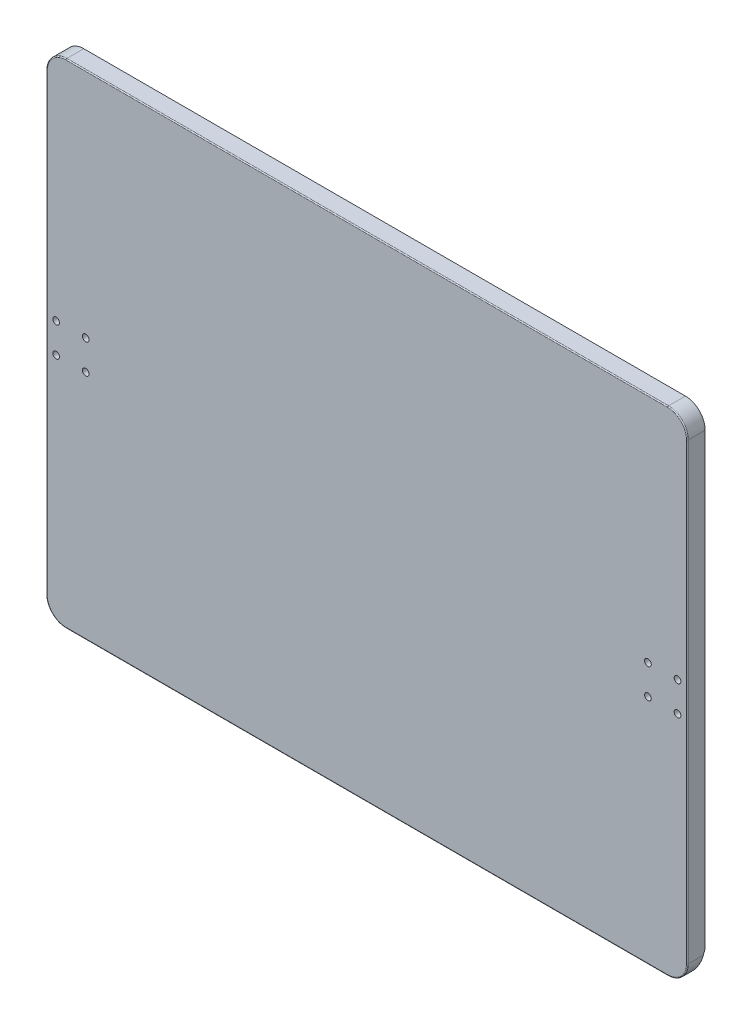
SolidWorks part; units mm, degrees
material "Beech"
ref_plane "Front Plane" through (0, 0, 0) normal (0, 0, 1) x (1, 0, 0)
ref_plane "Top Plane" through (0, 0, 0) normal (0, 1, 0) x (1, 0, 0)
ref_plane "Right Plane" through (0, 0, 0) normal (1, 0, 0) x (0, 0, -1)
sketch "Sketch1" plane through (0, 0, 0) normal (0, 0, 1) x (1, 0, 0)
  line L1 (0, 0) -> (650, 0)
  line L2 (0, 0) -> (0, 500)
  line L3 (0, 500) -> (650, 500)
  line L4 (650, 0) -> (650, 500)
  dimension "D1" = 500
  dimension "D2" = 650
extrude "base" add sketch "Sketch1" along normal blind 18
hole_wizard "counterbored M5 bolt holes" positions "Sketch2" profile "Sketch3" hole size "1/4" standard "ANSI Inch" end condition through all
sketch "Sketch2" plane through (0, 0, 18) normal (0, 0, 1) x (1, 0, 0)
  line L1 (10, 265) -> (40, 265)
  line L2 (10, 265) -> (10, 235)
  line L3 (10, 235) -> (40, 235)
  line L4 (40, 265) -> (40, 235)
  line L5 (10, 250) -> (0, 250)
  line L6 (0, 500) -> (0, 0) construction
  point P1 (10, 265)
  point P2 (40, 235)
  point P41 (10, 235)
  point P42 (40, 265)
  dimension "D1" = 30
  dimension "D2" = 30
  dimension "D3" = 10
sketch "Sketch3" plane through (10, 265, 18) normal (1, 0, 0) x (0, -1, 0)
  line L0 (0, 0) -> (0, 18)
  line L1 (0, 18) -> (3.3782, 18)
  line L2 (3.3782, 18) -> (3.3782, 0)
  line L5 (3.3782, 0) -> (0, 0)
  line L11 (0, -6.35) -> (0, 107.95) construction
  dimension "Thru Hole Dia." = 6.7564
  dimension "Thru Hole Depth" = 18
ref_plane "midplane in x" through (325, 0, 0) normal (-1, 0, 0) x (0, 0, 1)
mirror "mirror counterbored bolt holes" about plane through (325, 0, 0) normal (-1, 0, 0) of "counterbored M5 bolt holes"
fillet "round corners" radius 20 4 edges at (0, 500, 9) (650, 500, 9) (650, 0, 9) (0, 0, 9)
fillet "break top edge" radius 1 8 edges at (5.8579, 494.1421, 18) (325, 500, 18) (644.1421, 494.1421, 18) (650, 250, 18) (644.1421, 5.8579, 18) (325, 0, 18) (5.8579, 5.8579, 18) (0, 250, 18)
chamfer "front shadow chamfer" distance 25 angle 20 1 edges at (325, 0, 0) tangent propagation no first distance on face at (643.3782, 265, 0)
fillet "round chamfer edges" [suppressed] radius 1
equation "\"board_thickness\" = 18mm"
equation "\"way_width\"= 75mm"
equation "\"way_thickness\"= 50mm"
equation "\"radial_clearance\"= 0.1mm"
equation "\"slider_width\"= \"way_width\"-2* \"radial_clearance\""
equation "\"slider_thickness\" = \"way_thickness\" - 2 * \"radial_clearance\""
equation "\"column_width\"= \"way_width\" + 2 * \"board_thickness\""
equation "\"boxway_slot_width\" = 50mm"
equation "\"keeper_rail_width\" = (\"column_width\" - \"boxway_slot_width\")/2"
equation "\"slider_length\" = 125mm"
equation "\"nut_diameter\"= 22mm"
equation "\"nut_length\"= 15mm"
equation "\"leadscrew_diameter\"= 10mm"
equation "\"leadscrew_radial_clearance\"= 1mm"
equation "\"bearing_bolt_pattern_width\" = 30mm"
equation "\"bearing_bolt_pattern_height\" = 75mm"
equation "\"desktop_bolt_pattern_width\" = 30mm"
equation "\"desktop_bolt_pattern_height\" = 30mm"
equation "\"bearing_bolt_nut_counterbore_diameter\" = 12mm"
equation "\"bearing_bolt_nut_counterbore_depth\"= 10mm"
equation "\"desktop_depth\"= 500mm"
equation "\"desktop_width\"= 650mm"
equation "\"D1@Sketch1\"=\"desktop_depth\""
equation "\"D2@Sketch1\"=\"desktop_width\""
equation "\"desktop_thickness\"= 18mm"
equation "\"D1@base\" = \"desktop_thickness\""
equation "\"D1@Sketch2\"=\"desktop_bolt_pattern_height\""
equation "\"D2@Sketch2\"=\"desktop_bolt_pattern_width\""
